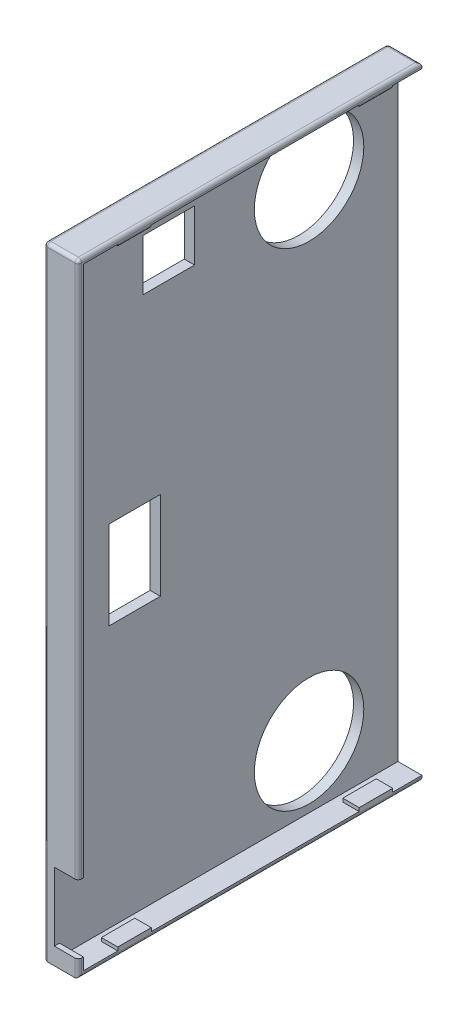
SolidWorks part; units mm, degrees
ref_plane "Plano frontal" through (0, 0, 0) normal (1, 0, 0) x (0, 1, 0)
ref_plane "Plano superior" through (0, 0, 0) normal (0, 0, 1) x (0, 1, 0)
ref_plane "Plano direito" through (0, 0, 0) normal (0, 1, 0) x (-1, 0, 0)
sketch "Esboço1" plane through (0, 0, 0) normal (1, 0, 0) x (0, 1, 0)
  line L1 (91, -51.75) -> (-91, -51.75)
  line L2 (91, -51.75) -> (91, 51.75)
  line L3 (91, 51.75) -> (-91, 51.75)
  line L4 (-91, -51.75) -> (-91, 51.75)
  line L5 (91, -51.75) -> (-91, 51.75) construction
  line L6 (91, 51.75) -> (-91, -51.75) construction
  point P0 (0, 0)
  dimension "D1" = 182
  dimension "D2" = 103.5
extrude "Ressalto-extrusão1" add sketch "Esboço1" along normal blind 10
sketch "Esboço2" plane through (10, 0, 0) normal (1, 0, 0) x (0, 1, 0)
  line L1 (89.5, -50.25) -> (-89.5, -50.25)
  line L2 (89.5, -50.25) -> (89.5, 50.25)
  line L3 (89.5, 50.25) -> (-89.5, 50.25)
  line L4 (-89.5, -50.25) -> (-89.5, 50.25)
  line L5 (89.5, -50.25) -> (-89.5, 50.25) construction
  line L6 (89.5, 50.25) -> (-89.5, -50.25) construction
  point P0 (0, 0)
  dimension "D1" = 179
  dimension "D2" = 100.5
extrude "Corte-extrusão1" cut sketch "Esboço2" against normal blind 7
sketch "Esboço4" plane through (0, -89.5, 0) normal (0, 1, 0) x (-1, 0, 0)
  line L0 (-10, 50.25) -> (-10, -50.25) construction
  line L1 (-10, 40.2) -> (-5.2, 40.2)
  line L2 (-10, 40.2) -> (-10, 30.4)
  line L3 (-10, 30.4) -> (-5.2, 30.4)
  line L4 (-5.2, 40.2) -> (-5.2, 30.4)
  line L5 (-3, 50.25) -> (-10, 50.25) construction
  dimension "D1" = 9.8
  dimension "D2" = 4.8
  dimension "D3" = 10.05
extrude "Ressalto-extrusão2" add sketch "Esboço4" along normal blind 1 contours L1 L4 L3 L2
mirror "Espelhar1" about plane through (0, 0, 0) normal (0, 0, 1) of "Ressalto-extrusão2"
mirror "Espelhar2" about plane through (0, 0, 0) normal (0, 1, 0) of "Espelhar1"
sketch "Esboço5" plane through (0, 0, -51.75) normal (0, 0, -1) x (1, 0, 0)
  line L1 (0, 91) -> (10, 91)
  line L2 (0, 91) -> (0, -91)
  line L3 (0, -91) -> (10, -91)
  line L4 (10, 91) -> (10, -91)
extrude "Corte-extrusão2" cut sketch "Esboço5" against normal blind 3
fillet "Filete3" radius 1 10 edges at (5, -91, -48.75) (5, 91, -48.75) (10, 91, 1.5) (10, -91, 1.5) (10, 0, 51.75) (0, -91, 1.5) (0, 0, -48.75) (0, 91, 1.5) (0, 0, 51.75) (5, 91, 51.75)
fillet "Filete8" radius 1 8 edges at (7.6, 88.5, -40.2) (5.2, 88.5, -35.3) (7.6, 88.5, -30.4) (10, 88.5, -35.3) (7.6, 88.5, 30.4) (5.2, 88.5, 35.3) (7.6, 88.5, 40.2) (10, 88.5, 35.3)
sketch "Esboço6" plane through (0, 0, 0) normal (-1, 0, 0) x (0, -1, 0)
  line L0 (-90, -47.75) -> (90, -47.75) construction
  circle A0 centre (-71.25, -22.75) radius 16
  dimension "D3" = 32
  dimension "D1" = 71.25
  dimension "D2" = 25
extrude "Corte-extrusão3" cut sketch "Esboço6" against normal blind 10
mirror "Espelhar3" about plane through (0, 0, 0) normal (0, 1, 0) of "Corte-extrusão3"
sketch "Esboço7" plane through (0, 0, 0) normal (-1, 0, 0) x (0, -1, 0)
  line L0 (90, 50.75) -> (-90, 50.75) construction
  line L1 (12.9, 20.75) -> (-12.9, 20.75)
  line L2 (12.9, 20.75) -> (12.9, 35.75)
  line L3 (12.9, 35.75) -> (-12.9, 35.75)
  line L4 (-12.9, 20.75) -> (-12.9, 35.75)
  line L5 (12.9, 20.75) -> (-12.9, 35.75) construction
  line L6 (12.9, 35.75) -> (-12.9, 20.75) construction
  point P0 (0, 28.25)
  dimension "D1" = 25.8
  dimension "D2" = 15
  dimension "D3" = 15
extrude "Corte-extrusão4" cut sketch "Esboço7" against normal blind 10
sketch "Esboço9" plane through (3, 0, 0) normal (1, 0, 0) x (0, 1, 0)
  line L0 (89.5, 50.25) -> (-89.5, 50.25) construction
  line L1 (81, 10.75) -> (66, 10.75)
  line L2 (81, 10.75) -> (81, 25.75)
  line L3 (81, 25.75) -> (66, 25.75)
  line L4 (66, 10.75) -> (66, 25.75)
  line L5 (81, 10.75) -> (66, 25.75) construction
  line L6 (81, 25.75) -> (66, 10.75) construction
  line L7 (89.5, -48.75) -> (89.5, 50.25) construction
  point P0 (73.5, 18.25)
  dimension "D1" = 24.5
  dimension "D2" = 8.5
  dimension "D3" = 15
  dimension "D4" = 15
extrude "Corte-extrusão5" cut sketch "Esboço9" against normal blind 10
sketch "Esboço10" plane through (0, 0, 51.75) normal (0, 0, 1) x (1, 0, 0)
  line L1 (10.8359, -86) -> (3, -86)
  line L2 (10.8359, -86) -> (10.8359, -66)
  line L3 (10.8359, -66) -> (3, -66)
  line L4 (3, -86) -> (3, -66)
  line L6 (9, -91) -> (1, -91) construction
  line L7 (0, -90) -> (0, 90) construction
  point P4 (10.8359, -86)
  point P5 (2.3866, -66)
  dimension "D1" = 5
  dimension "D2" = 20
  dimension "D3" = 3
extrude "Corte-extrusão6" cut sketch "Esboço10" against normal blind 10
